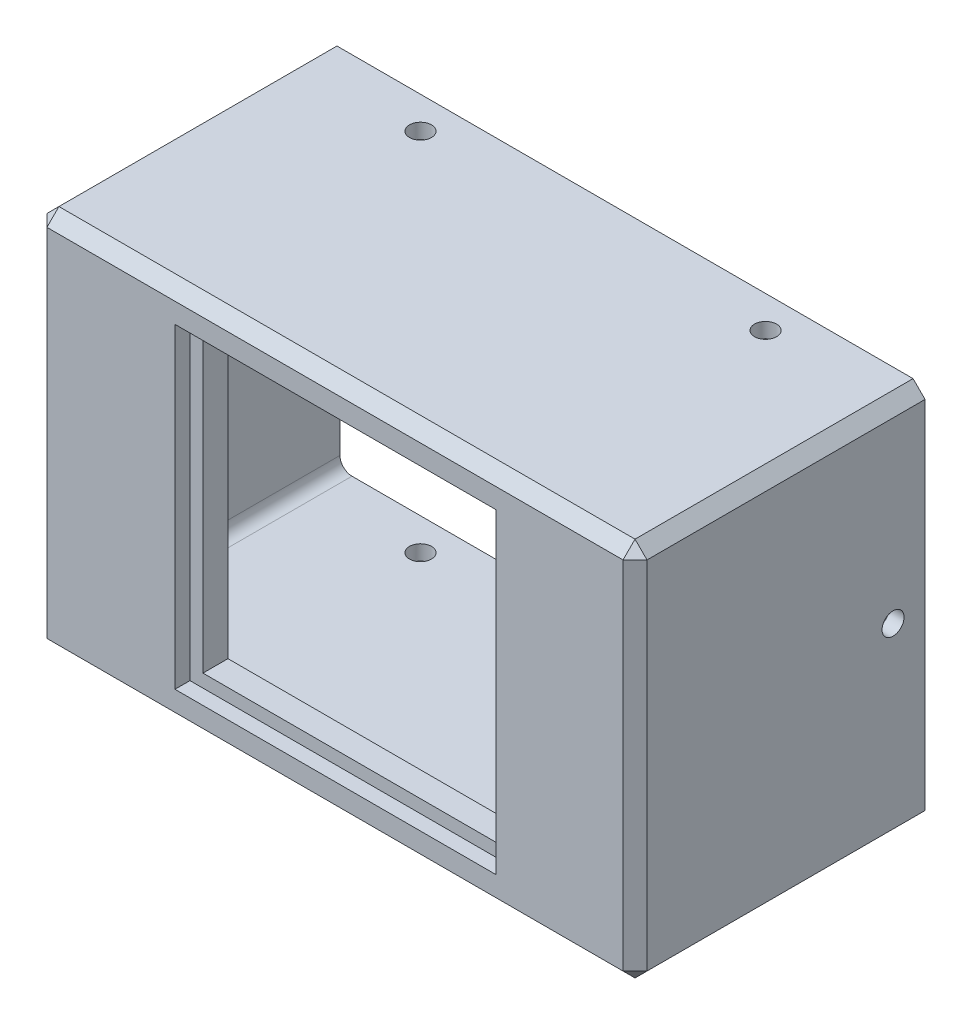
SolidWorks part; units mm, degrees
ref_plane "Plan de face" through (0, 0, 0) normal (0, 0, 1) x (1, 0, 0)
ref_plane "Plan de dessus" through (0, 0, 0) normal (0, 1, 0) x (1, 0, 0)
ref_plane "Plan de droite" through (0, 0, 0) normal (1, 0, 0) x (0, 0, -1)
sketch "Esquisse1" plane through (0, 0, 0) normal (0, 0, 1) x (1, 0, 0)
  line L1 (30, 19) -> (-30, 19)
  line L2 (30, 19) -> (30, -19)
  line L3 (30, -19) -> (-30, -19)
  line L4 (-30, 19) -> (-30, -19)
  line L5 (30, 19) -> (-30, -19) construction
  line L6 (30, -19) -> (-30, 19) construction
  point P0 (0, 0)
  point P6 (0, 0)
  dimension "D1" = 60
  dimension "D2" = 38
extrude "BASE" add sketch "Esquisse1" along normal blind 4
sketch "Esquisse2" plane through (0, 0, 4) normal (0, 0, 1) x (1, 0, 0)
  line L0 (-21.2, 0) -> (26.8, 0) construction
  line L1 (26.8, 16.5) -> (-21.2, 16.5) construction
  line L2 (26.8, 16.5) -> (26.8, -16.5) construction
  line L3 (26.8, -16.5) -> (-21.2, -16.5) construction
  line L4 (-21.2, 16.5) -> (-21.2, -16.5) construction
  line L5 (26.8, 16.5) -> (-21.2, -16.5) construction
  line L6 (26.8, -16.5) -> (-21.2, 16.5) construction
  line L7 (-14.7, 14.5) -> (14.8, 14.5)
  line L8 (-14.7, 14.5) -> (-14.7, -14.5)
  line L9 (-14.7, -14.5) -> (14.8, -14.5)
  line L10 (14.8, 14.5) -> (14.8, -14.5)
  line L11 (30, -19) -> (30, 19) construction
  point P0 (0, 0)
  dimension "D1" = 33
  dimension "D2" = 48
  dimension "D3" = 6.5
  dimension "D4" = 2
  dimension "D5" = 2
  dimension "D6" = 12
  dimension "D7" = 3.2
extrude "Screen" cut sketch "Esquisse2" against normal up to surface (4 mm away) up to face at (0, 0, 0)
sketch "Esquisse5" plane through (0, 0, 0) normal (0, 0, -1) x (-1, 0, 0)
  line L0 (2.2, 0) -> (-2.2, 0) construction
  line L1 (21.1, 16.5) -> (-26.8, 16.5) construction
  line L2 (21.1, 16.5) -> (21.1, -16.5) construction
  line L3 (21.1, -16.5) -> (-26.8, -16.5) construction
  line L4 (-26.8, 16.5) -> (-26.8, -16.5) construction
  line L5 (21.1, 16.5) -> (-26.8, -16.5) construction
  line L6 (21.1, -16.5) -> (-26.8, 16.5) construction
  line L8 (-2.85, 16.5) -> (-2.85, -16.5) construction
  circle A1 centre (-24.3, 14) radius 2.1
  circle A2 centre (-24.3, -14) radius 2.1
  circle A3 centre (18.6, -14) radius 2.1
  circle A4 centre (18.6, 14) radius 2.1
  point P0 (-0.9161, -1.3324)
  dimension "D3" = 4.2
  dimension "D1" = 47.9
  dimension "D2" = 33
  dimension "D4" = 2.5
  dimension "D5" = 2.5
extrude "Inserts_M3" cut sketch "Esquisse5" against normal blind 3
sketch "Esquisse6" plane through (0, 0, 0) normal (0, 0, -1) x (-1, 0, 0)
  line L0 (-28.5, 17.5) -> (-28.5, -17.5)
  line L1 (-30, 19) -> (30, 19)
  line L2 (-30, 19) -> (-30, -19)
  line L3 (-30, -19) -> (30, -19)
  line L4 (30, 19) -> (30, -19)
  line L5 (-28.5, -17.5) -> (28.5, -17.5)
  line L6 (28.5, 17.5) -> (28.5, -17.5)
  line L7 (-28.5, 17.5) -> (28.5, 17.5)
  dimension "D1" = 1.5
extrude "Walls" add sketch "Esquisse6" along normal blind 25
chamfer "Chanfrein_EXT" distance 1.2 angle 45 8 edges at (0, 19, 4) (30, 19, -10.5) (30, 0, 4) (30, -19, -10.5) (0, -19, 4) (-30, -19, -10.5) (-30, 0, 4) (-30, 19, -10.5)
fillet "Fillet_INT" radius 1.2 8 edges at (0, 17.5, 0) (28.5, 0, 0) (-28.5, 0, 0) (0, -17.5, 0) (-28.5, -17.5, -12.5) (-28.5, 17.5, -12.5) (28.5, -17.5, -12.5) (28.5, 17.5, -12.5)
sketch "Esquisse7" plane through (30, 0, 0) normal (1, 0, 0) x (0, 0, -1)
  line L0 (25, 17.8) -> (25, -17.8) construction
  line L1 (-2.8, 17.8) -> (-2.8, -17.8) construction
  circle A0 centre (21.8, 0) radius 1.1
  point P7 (-2.8, 0)
  dimension "D1" = 2.2
  dimension "D2" = 3.2
extrude "Passage_Vis_Horizontal" cut sketch "Esquisse7" against normal through all
sketch "Esquisse9" plane through (0, 19, 0) normal (0, 1, 0) x (1, 0, 0)
  line L0 (-28.8, 25) -> (28.8, 25) construction
  line L2 (30, 25) -> (30, -2.8) construction
  line L4 (-30, -2.8) -> (-30, 25) construction
  circle A0 centre (-17.25, 21.8) radius 1.1
  circle A1 centre (17.25, 21.8) radius 1.1
  dimension "D1" = 2.2
  dimension "D2" = 3.2
  dimension "D3" = 12.75
  dimension "D4" = 12.75
extrude "Passage_Vis_Vertical" cut sketch "Esquisse9" against normal through all
sketch "Esquisse11" plane through (0, 0, 4) normal (0, 0, 1) x (1, 0, 0)
  line L1 (-16, 15.8) -> (16.1, 15.8)
  line L2 (-16, 15.8) -> (-16, -15.8)
  line L3 (-16, -15.8) -> (16.1, -15.8)
  line L4 (16.1, 15.8) -> (16.1, -15.8)
  line L6 (-14.7, 14.5) -> (-14.7, -14.5) construction
  line L7 (-14.7, -14.5) -> (14.8, -14.5) construction
  line L8 (14.8, 14.5) -> (-14.7, 14.5) construction
  line L13 (14.8, -14.5) -> (14.8, 14.5) construction
  dimension "D1" = 1.3
  dimension "D2" = 1.3
  dimension "D3" = 1.3
  dimension "D4" = 1.3
extrude "Emplacement Verre 32.5*32" cut sketch "Esquisse11" against normal blind 1.5 contours L2 L3 L4 L1
equation "\"D2@Esquisse11\"=\"D1@Esquisse11\""
equation "\"D3@Esquisse11\"=\"D1@Esquisse11\""
equation "\"D4@Esquisse11\"=\"D1@Esquisse11\""
